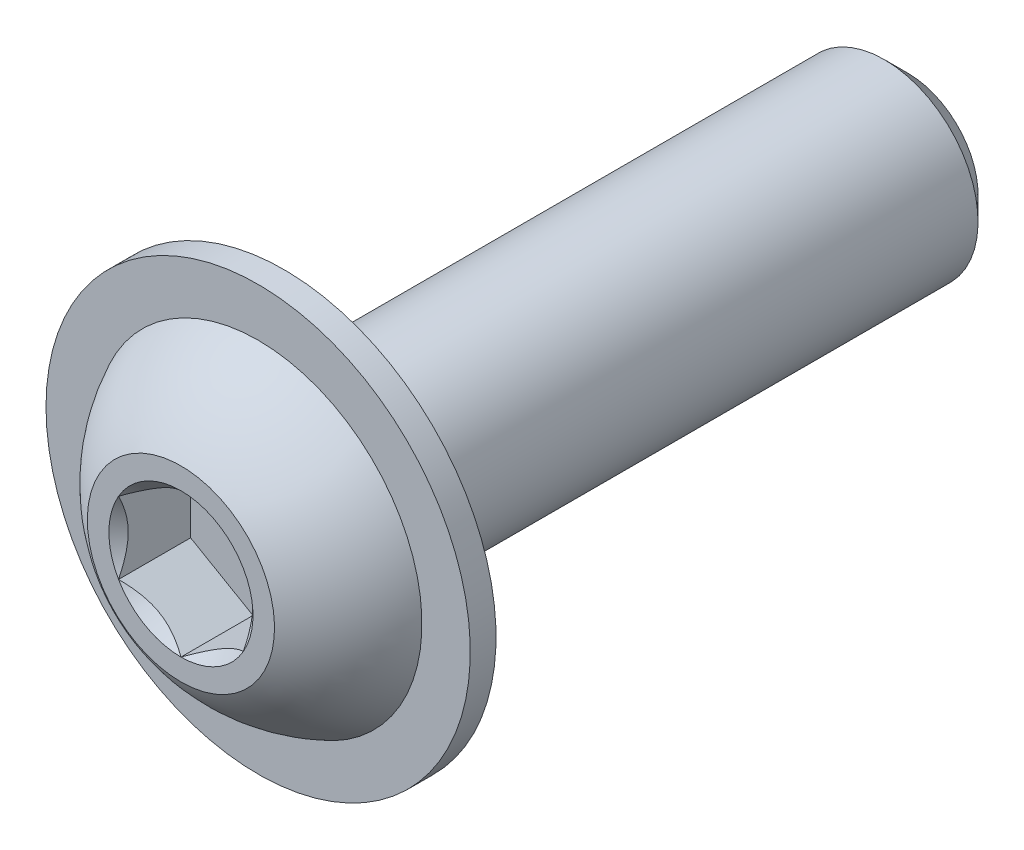
SolidWorks part; units mm, degrees
material "AISI 304"
ref_plane "Front" through (0, 0, 0) normal (0, 0, 1) x (1, 0, 0)
ref_plane "Top" through (0, 0, 0) normal (0, 1, 0) x (1, 0, 0)
ref_plane "Right" through (0, 0, 0) normal (1, 0, 0) x (0, 0, -1)
sketch "Sketch1" plane through (0, 0, 0) normal (1, 0, 0) x (0, 0, -1)
  line L2 (3.3, 3) -> (23.3, 3)
  line L3 (23.3, 3) -> (23.3, 0)
  line L4 (23.3, 0) -> (3.3, 0)
  line L6 (2.475, 5.25) -> (3.3, 5.25) construction
  line L7 (23.3, 3) -> (23.3, -3) construction
  line L8 (0, 0) -> (3.3, 0) construction
  line L9 (3.3, 5.25) -> (3.3, -5.25) construction
  line L11 (3.3, 3) -> (3.3, 0)
  line L13 (0, 2) -> (0, -2) construction
  line L14 (0, 2) -> (0, 3) construction
  line L15 (2.475, 5.25) -> (2.475, 6.8) construction
  line L16 (2.475, 6.8) -> (3.3, 6.8) construction
  line L17 (3.3, 6.8) -> (3.3, 5.25) construction
  line L18 (3.3, 6.8) -> (3.3, -6.8) construction
  arc A3 (0, 3) -> (2.475, 5.25) centre (4.9875, 0) cw construction
  dimension "D1" = 0.825
revolve "Revolve1" add sketch "Sketch1" angle 360 mid plane about L4
sketch "Sketch3" plane through (0, 0, -23.3) normal (0, 0, -1) x (-1, 0, 0)
  circle A0 centre (0, 0) radius 3
curve "Helix/Spiral1" pitch 1 height 21 turns 21
sketch "Sketch2" plane through (0, 0, 0) normal (1, 0, 0) x (0, 0, -1)
  line L0 (23.3, 3) -> (24.175, 3)
  line L1 (24.175, 3) -> (23.8, 2.3505)
  line L2 (23.8, 2.3505) -> (23.675, 2.3505)
  line L3 (23.675, 2.3505) -> (23.3, 3)
  line L4 (23.4875, 2.6752) -> (23.9875, 2.6752) construction
  dimension "D1" = 60
  dimension "D2" = 0.125
  dimension "D3" = 0.5
chamfer "Chamfer1" distance 0.75 angle 45 1 edges at (0, 3, -23.3)
sweep "Cut-Sweep1" [suppressed] cut profiles "Sketch2" path "Helix/Spiral1"
sketch "Sketch7" plane through (0, 0, 0) normal (1, 0, 0) x (0, 0, -1)
  line L6 (2.475, 5.25) -> (3.3, 5.25) construction
  line L8 (0, 0) -> (3.3, 0) construction
  line L11 (3.3, 5.25) -> (3.3, -5.25) construction
  line L12 (2.475, 5.25) -> (3.3, 5.25)
  line L13 (0, 0) -> (3.3, 0)
  line L14 (0, 2) -> (0, -2) construction
  line L15 (3.3, 5.25) -> (3.3, 0)
  line L16 (0, 3) -> (0, 0)
  arc A2 (2.475, 5.25) -> (0, 3) centre (4.9875, 0) ccw construction
  arc A3 (2.475, 5.25) -> (0, 3) centre (4.9875, 0) ccw
revolve "Revolve2" add sketch "Sketch7" angle 360 mid plane about L13
sketch "Sketch11" plane through (0, 0, -3.3) normal (0, 0, -1) x (-1, 0, 0)
  circle A0 centre (0, 0) radius 6.8
extrude "Boss-Extrude3" add sketch "Sketch11" against normal up to vertex (0.825 mm away) up to point (0, 5.25, -2.475)
sketch "Sketch5" plane through (0, 0, 0) normal (0, 0, 1) x (1, 0, 0)
  line L1 (2, -1.1547) -> (2, 1.1547)
  line L2 (2, 1.1547) -> (0, 2.3094)
  line L3 (0, 2.3094) -> (-2, 1.1547)
  line L4 (-2, 1.1547) -> (-2, -1.1547)
  line L5 (-2, -1.1547) -> (0, -2.3094)
  line L6 (0, -2.3094) -> (2, -1.1547)
  circle A0 centre (0, 0) radius 2 construction
extrude "Cut-Extrude2" cut sketch "Sketch5" against normal blind 2.31
sketch "Sketch6" plane through (0, 0, 0) normal (0, 0, 1) x (1, 0, 0)
  circle A0 centre (0, 0) radius 2.3094
extrude "Cut-Extrude3" cut sketch "Sketch6" against normal blind 2.31 draft 45
sketch "Sketch9" [suppressed] plane through (0, 0, -3.3) normal (0, 0, 1) x (1, 0, 0)
  circle A2 centre (0, 0) radius 3
extrude "Boss-Extrude2" [suppressed] add sketch "Sketch9" against normal offset from surface (6.35 mm away) 31.75 up to face at (0, 2.25, -23.3)
sketch "Sketch10" plane through (0, 0, 0) normal (1, 0, 0) x (0, 0, -1)
  line L0 (23.3, 3) -> (23.3, -3) construction
  point P0 (21.8, -3)
  dimension "D1" = 1.5
equation "\"D3@Helix/Spiral1\" = \"Lg@Sketch1\" + \"D4@Helix/Spiral1\""
equation "\"D2@Sketch2\" = \"D4@Helix/Spiral1\" * .125"
equation "\"D3@Sketch2\" = \"D4@Helix/Spiral1\" * .5"
equation "\"D1@Chamfer1\" = \"D4@Helix/Spiral1\" * .75"
equation "\"D1@Cut-Extrude2\" = \"Head Ht@Sketch1\" * .7"
equation "\"D1@Sketch1\" = \"Head Ht@Sketch1\" * .25"
equation "\"D1@Sketch10\" = \"D4@Helix/Spiral1\" * 1.5"
equation "\"D1@Cut-Extrude3\" = \"D1@Cut-Extrude2\""
